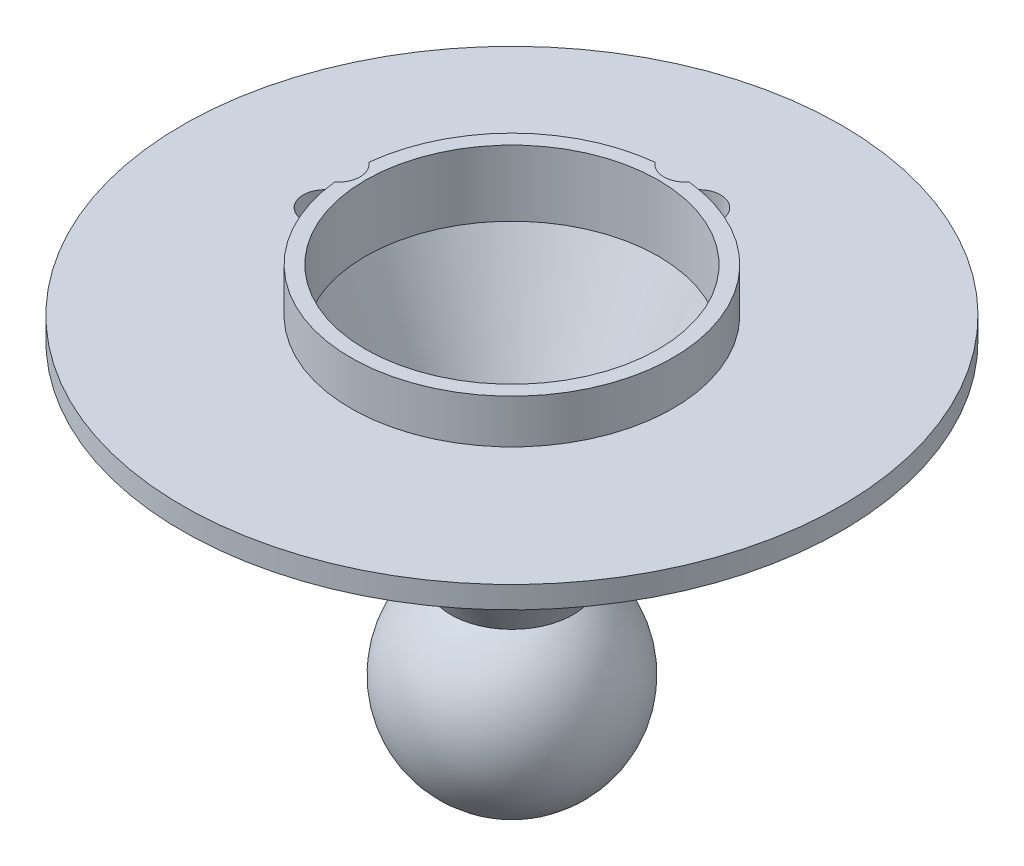
SolidWorks part; units mm, degrees
ref_plane "Ebene vorne" through (0, 0, 0) normal (0, 0, 1) x (1, 0, 0)
ref_plane "Ebene oben" through (0, 0, 0) normal (0, 1, 0) x (1, 0, 0)
ref_plane "Ebene rechts" through (0, 0, 0) normal (1, 0, 0) x (0, 0, -1)
sketch "Sketch1" plane through (0, 0, 0) normal (0, 0, 1) x (1, 0, 0)
  line L0 (-6.8329, 22.5) -> (-6.8329, 0)
  line L1 (-6.8329, 22.5) -> (-20, 50.7369)
  line L3 (-24.6355, 50.7369) -> (-8.3329, 22.5)
  line L5 (-8.3329, 0) -> (-6.8329, 0)
  line L6 (0, -17.7734) -> (0, 75.1802) construction
  line L7 (0, 11.25) -> (-8.3329, 22.5) construction
  line L8 (0, 11.25) -> (-8.3329, 0) construction
  line L9 (-24.6355, 50.7369) -> (-45, 50.7369)
  line L10 (-45, 50.7369) -> (-45, 53.7369)
  line L11 (-45, 53.7369) -> (-22, 53.7369)
  line L12 (-20, 59.7369) -> (-20, 50.7369)
  line L14 (-20, 59.7369) -> (-22, 59.7369)
  line L15 (-22, 59.7369) -> (-22, 53.7369)
  arc A1 (-8.3329, 22.5) -> (-8.3329, 0) centre (0, 11.25) ccw
  dimension "D8" = 14
  dimension "D5" = 25
  dimension "D1" = 30
  dimension "D2" = 1.5
  dimension "D3" = 1.5
  dimension "D4" = 20
  dimension "D6" = 22.5
  dimension "D7" = 0
  dimension "D9" = 1.5
  dimension "D10" = 3
  dimension "D11" = 2
  dimension "40" = 45
  dimension "D12" = 6
revolve "Revolve1" add sketch "Sketch1" angle 360 about L6
sketch "Sketch2" plane through (0, 53.7369, 0) normal (0, 1, 0) x (1, 0, 0)
  line L2 (0, 0) -> (-22.5, 0) construction
  line L3 (-28.5, 0) -> (-39.5123, 0) construction
  line L4 (-25.5, 3) -> (-23.75, 3)
  line L5 (-25.5, -3) -> (-23.6513, -3)
  arc A1 (-25.5, 3) -> (-25.5, -3) centre (-25.5, 0) ccw
  arc A2 (-23.75, -3) -> (-23.75, 3) centre (-23.75, 0) ccw
  circle M7 centre (0, 0) radius 22
  dimension "D1" = 6
extrude "Cut-Extrude1" cut sketch "Sketch2" against normal up to next and the other way blind 10 contours L5 A2 L4 A1 M7 | A2 M7 region at (-24.9945, 53.7369, 0) region at (-21.4658, 53.7369, 0)
pattern_circular "CirPattern1" count 2 every 90 about axis through (0, 22.5, 0) along (0, -1, 0) of "Cut-Extrude1"
